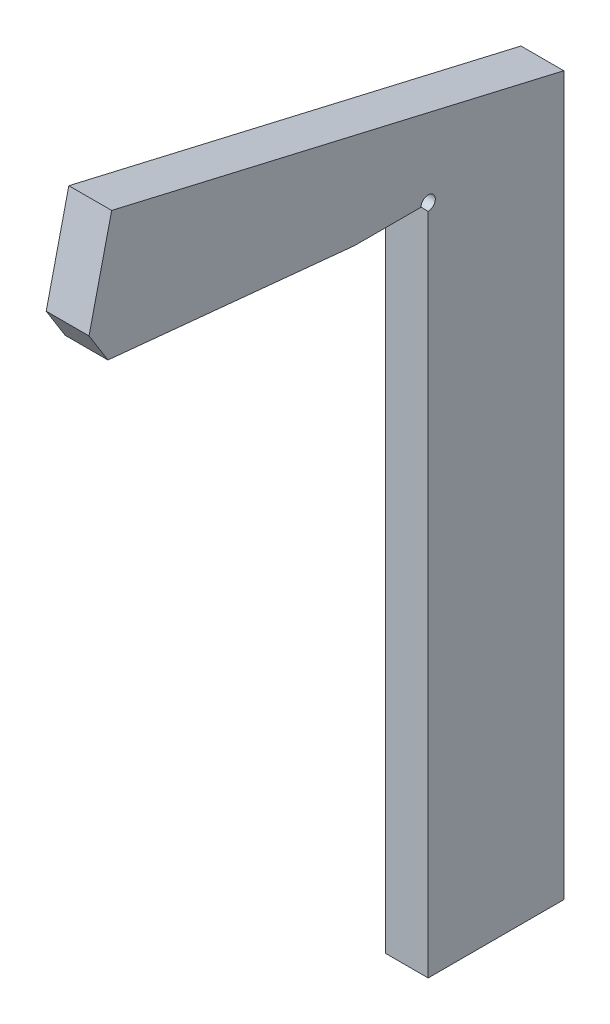
SolidWorks part; units mm, degrees
material "MDF"
ref_plane "Front Plane" through (0, 0, 0) normal (0, 0, 1) x (1, 0, 0)
ref_plane "Top Plane" through (0, 0, 0) normal (0, 1, 0) x (1, 0, 0)
ref_plane "Right Plane" through (0, 0, 0) normal (1, 0, 0) x (0, 0, -1)
sketch "Sketch2" plane through (-113.7888, 0, 0) normal (1, 0, 0) x (0, 0, -1)
  line L17 (0, 20.8246) -> (-83.8286, 40.3069)
  line L18 (0, 20.8246) -> (-83.8286, 40.3069)
  line L29 (-83.8286, 40.3069) -> (-93.1962, 0)
  line L30 (-83.8286, 40.3069) -> (-93.1962, 0)
  line L31 (-93.1962, 0) -> (-63.5, 0)
  line L32 (-93.1962, 0) -> (-63.5, 0)
  line L46 (0, -298.45) -> (-60.325, -298.45)
  line L47 (0, -363.22) -> (0, -433.07) construction
  line L48 (-28.575, -298.45) -> (0, -298.45) construction
  line L53 (-28.575, -447.675) -> (-28.575, -450.85)
  line L54 (-28.575, -450.85) -> (0, -450.85)
  line L55 (0, -450.85) -> (0, 20.8246)
  line L57 (-60.325, -3.175) -> (-60.325, -412.75)
  line L60 (0, -298.45) -> (0, 20.8246)
  line L62 (-60.325, -3.175) -> (-60.325, -298.45)
  arc A14 (-60.325, -3.175) -> (-63.5, 0) centre (-60.325, 0) ccw
  arc A15 (-60.325, -412.75) -> (-31.746, -444.3413) centre (-28.575, -412.75) ccw
  arc A16 (-28.575, -447.675) -> (-31.746, -444.3413) centre (-28.575, -444.5) ccw
  arc A17 (-60.325, -3.175) -> (-63.5, 0) centre (-60.325, 0) ccw
  dimension "D2" = 0
extrude "Boss-Extrude1" add sketch "Sketch2" along normal blind 19.05
sketch "Sketch3" plane through (-113.7888, 0, 0) normal (-1, 0, 0) x (0, 0, 1)
  line L0 (83.8286, 40.3069) -> (201.0857, 67.5582)
  line L1 (495.3358, 135.9439) -> (66.675, 36.3203) construction
  line L2 (201.0857, 67.5582) -> (214.0229, 11.8918)
  line L7 (83.8286, 40.3069) -> (93.1962, 0)
  line L8 (93.1962, 0) -> (214.0229, 11.8918)
  arc A0 (63.5, 0) -> (60.325, -3.175) centre (60.325, 0) ccw construction
  dimension "D1" = 57.15
  dimension "D2" = 152.4
extrude "Boss-Extrude2" add sketch "Sketch3" against normal through all
chamfer "Chamfer1" distance 12.7 angle 45 1 edges at (-104.2638, 11.8918, 214.0229) first distance on face at (-104.2638, 39.725, 207.5543)
